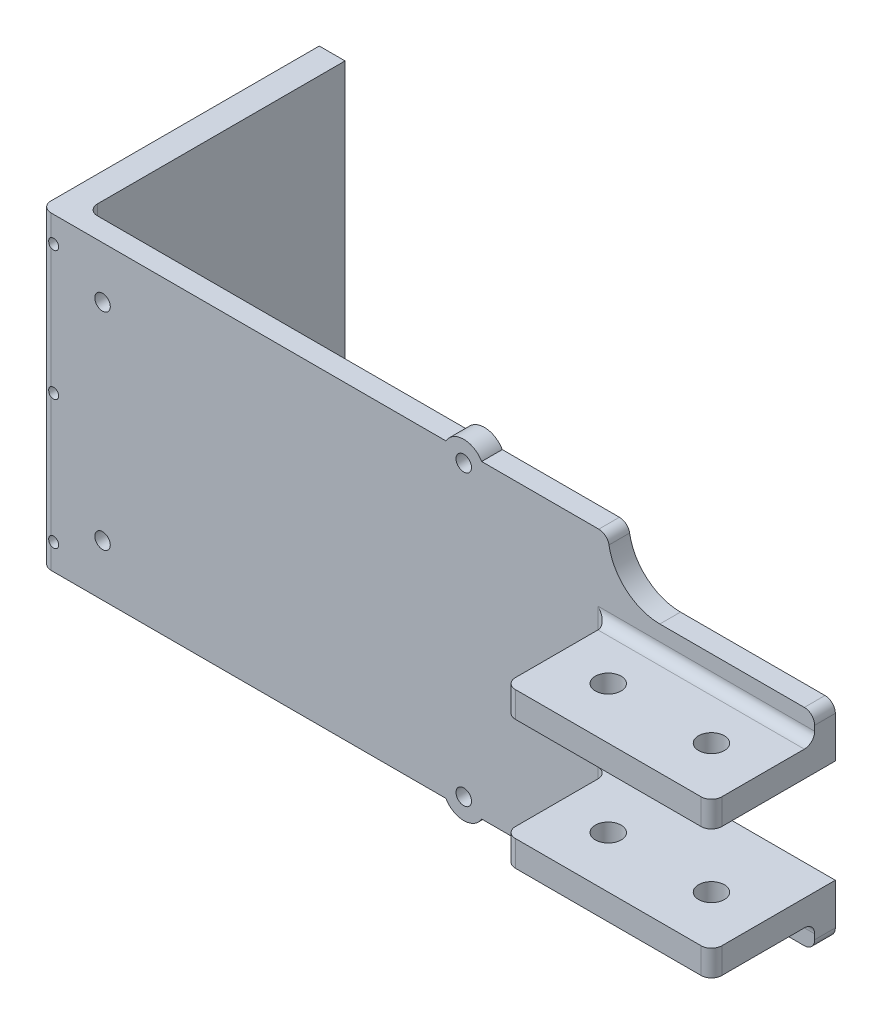
SolidWorks part; units mm, degrees
ref_plane "Piano frontale" through (0, 0, 0) normal (0, 0, 1) x (1, 0, 0)
ref_plane "Piano superiore" through (0, 0, 0) normal (0, 1, 0) x (1, 0, 0)
ref_plane "Piano destro" through (0, 0, 0) normal (1, 0, 0) x (0, 0, -1)
sketch "Schizzo1" plane through (0, 0, 0) normal (0, 0, 1) x (1, 0, 0)
  line L0 (72.5, -10) -> (32.5, -10)
  line L1 (-72.5, 20) -> (72.5, 20)
  line L2 (-72.5, 20) -> (-72.5, -20)
  line L3 (-72.5, -20) -> (72.5, -20)
  line L4 (72.5, 20) -> (72.5, -20)
  line L5 (-72.5, 20) -> (72.5, -20) construction
  line L6 (-72.5, -20) -> (72.5, 20) construction
  line L7 (72.5, -10) -> (72.5, 10)
  line L8 (32.5, -10) -> (32.5, 10)
  line L9 (72.5, 10) -> (32.5, 10)
  line L10 (0, 0) -> (50000, 0) construction
  line L11 (-72.5, -30) -> (-72.5, 30)
  line L12 (-72.5, -30) -> (32.5, -30)
  line L13 (-72.5, 30) -> (32.5, 30)
  line L14 (32.5, -30) -> (32.5, 30)
  line L15 (-65.5, -3.5519) -> (-65.5, -50003.5519) construction
  line L16 (4.5, -3.6336) -> (4.5, -50003.6336) construction
  circle A0 centre (-65.5, -20) radius 1.5
  circle A1 centre (4.5, -28) radius 1.5
  circle A2 centre (4.5, 28) radius 1.5
  circle A3 centre (-65.5, 20) radius 1.5
  point P0 (0, 0)
  point P12 (32.5, 0)
  point P13 (32.5, 0)
  point P26 (11.1871, -40.5359)
  dimension "D7" = 3
  dimension "D8" = 3
  dimension "D1" = 40
  dimension "D2" = 20
  dimension "D3" = 40
  dimension "D5" = 60
  dimension "D6" = 105
  dimension "D9" = 70
  dimension "D10" = 20
  dimension "D11" = 28
  dimension "D12" = 7
extrude "Estrusione-Estrusione1" add sketch "Schizzo1" along normal blind 4 contours L1 A3 L2 L3 A0 L14 L8 | L1 A3 L14 L13 L11 A2 | A0 L3 L11 L12 L14 A1 | L14 L9 L4 L1 | L14 L3 L4 L0 region at (52.5, -15, 0) region at (-19.9233, 0, 0) region at (52.5, 15, 0) region at (-20.0119, -24.9944, 0) region at (-20.0119, 24.9944, 0)
fillet "Raccordo1" radius 10 2 edges at (32.5, 20, 2) (32.5, -20, 2)
sketch "Schizzo2" plane through (0, 0, 4) normal (0, 0, 1) x (1, 0, 0)
  circle A0 centre (4.5, -28) radius 2
  circle A1 centre (4.5, -28) radius 4
  circle A2 centre (4.5, 28) radius 2
  circle A3 centre (4.5, 28) radius 4
  dimension "D1" = 8
  dimension "D2" = 8
extrude "Estrusione-Estrusione2" add sketch "Schizzo2" against normal blind 4
sketch "Schizzo3" plane through (0, 0, 4) normal (0, 0, 1) x (1, 0, 0)
  line L0 (72.5, -10) -> (32.5, -10)
  line L1 (32.5, -10) -> (32.5, -15)
  line L2 (32.5, -15) -> (72.5, -15)
  line L3 (72.5, -10) -> (72.5, -20) construction
  line L4 (72.5, -15) -> (72.5, -10)
  line L5 (0, 0) -> (50000, 0) construction
  line L6 (72.5, 15) -> (72.5, 10)
  line L7 (32.5, 15) -> (72.5, 15)
  line L8 (32.5, 10) -> (32.5, 15)
  line L9 (72.5, 10) -> (32.5, 10)
  dimension "D1" = 5
extrude "Estrusione-Estrusione3" add sketch "Schizzo3" along normal blind 20
sketch "Schizzo4" plane through (0, -15, 0) normal (0, -1, 0) x (1, 0, 0)
  line L0 (30, 14) -> (50030, 14) construction
  line L1 (32.5, 24) -> (32.5, 4) construction
  line L2 (42.5, 24) -> (42.5, -49976) construction
  line L4 (62.5, 24) -> (62.5, -49976) construction
  line L6 (72.5, 24) -> (72.5, 4) construction
  circle A0 centre (42.5, 14) radius 2.5
  circle A1 centre (62.5, 14) radius 2.5
  point P4 (32.5, 14)
  point P15 (0, 0)
  point P16 (0, 0)
  dimension "D3" = 5
  dimension "D4" = 5
  dimension "D1" = 20
  dimension "D2" = 10
extrude "Taglio-Estrusione1" cut sketch "Schizzo4" against normal through all and the other way through all
sketch "Schizzo5" plane through (0, 0, 4) normal (0, 0, 1) x (1, 0, 0)
  line L0 (-72.5, -30) -> (-72.5, 30)
  line L1 (-72.5, -30) -> (-77.5, -30)
  line L2 (-72.5, 30) -> (-77.5, 30)
  line L3 (-77.5, -30) -> (-77.5, 30)
  dimension "D1" = 5
extrude "Estrusione-Estrusione4" add sketch "Schizzo5" against normal blind 54
sketch "Schizzo6" plane through (0, 0, -50) normal (0, 0, -1) x (-1, 0, 0)
  line L0 (72.5, 30) -> (72.5, -30)
  line L1 (72.5, 30) -> (87.5, 30)
  line L2 (72.5, -30) -> (87.5, -30)
  line L3 (87.5, 30) -> (87.5, -30)
  line L4 (82.0659, 30) -> (82.0659, -30) construction
  line L5 (87.5, 0) -> (-49912.5, 0) construction
  line L6 (77.5, 30) -> (87.5, 20)
  line L7 (77.5, -30) -> (87.5, -20)
  circle A0 centre (82.0659, 15) radius 1.5
  circle A1 centre (82.0659, -15) radius 1.5
  point P14 (87.5, 0)
  line M8 (77.5, -30) -> (77.5, 30)
  dimension "D2" = 3
  dimension "D3" = 3
  dimension "D1" = 15
  dimension "D4" = 30
  dimension "D5" = 15
  dimension "D6" = 45
  dimension "D7" = 45
extrude "Estrusione-Estrusione5" add sketch "Schizzo6" against normal blind 5 contours L7 L3 L6 A1 A0 M8 region at (-82.1696, 0, -50)
fillet "Raccordo2" radius 2 16 edges at (32.5, -12.5, 24) (72.5, -12.5, 24) (72.5, 12.5, 24) (32.5, 12.5, 24) (-87.5, 20, -47.5) (-87.5, -20, -47.5) (-72.5, 0, 0) (-77.5, 0, 4) (32.5, 12.5, 4) (32.5, -12.5, 4) (32.5, 30, 2) (72.5, 20, 2) (72.5, -20, 2) (32.5, -30, 2) (52.5, -15, 4) (52.5, 15, 4)
chamfer "Smusso1" distance 1 angle 45 4 edges at (-64, -20, 0) (-64, 20, 0) (6, 28, 0) (6, -28, 0)
sketch "Schizzo7" plane through (0, 0, 4) normal (0, 0, 1) x (1, 0, 0)
  line L0 (-75, -30) -> (-75, 49970) construction
  line L2 (-77.5, -30) -> (-77.5, 30) construction
  line L3 (0, 0) -> (-50000, 0) construction
  circle A0 centre (-75, 0) radius 1
  circle A1 centre (-75, 25) radius 1
  circle A2 centre (-75, -25) radius 1
  dimension "D2" = 2
  dimension "D3" = 2
  dimension "D4" = 2
  dimension "D1" = 2.5
  dimension "D5" = 25
  dimension "D6" = 25
extrude "Taglio-Estrusione2" cut sketch "Schizzo7" against normal blind 10
